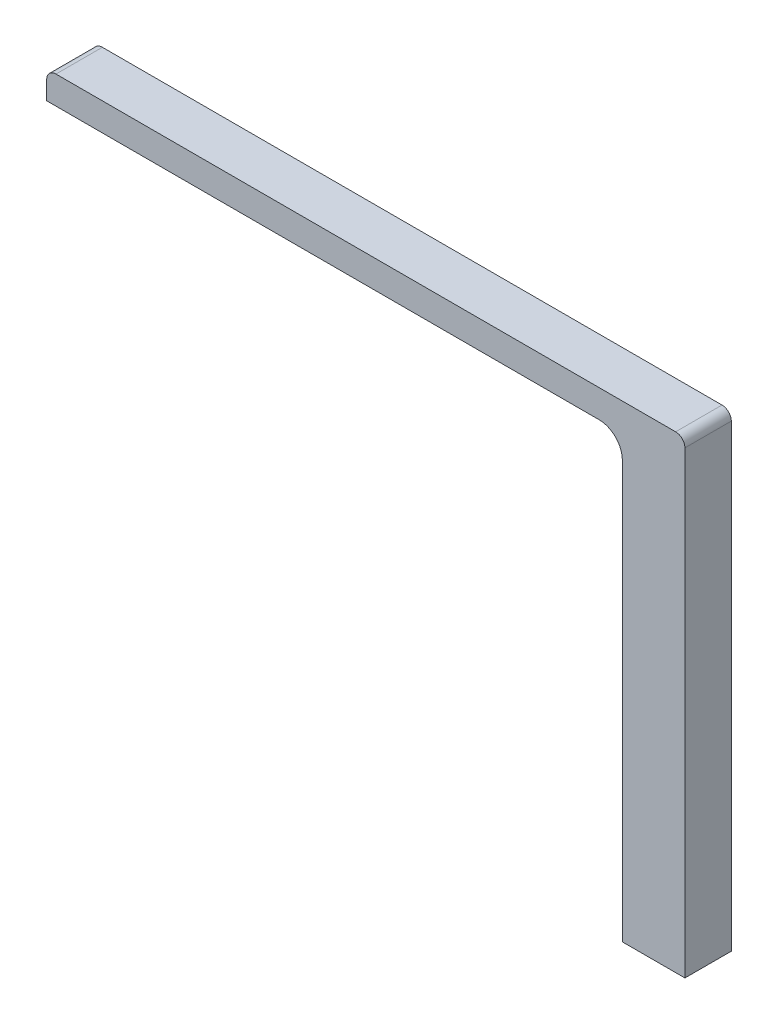
SolidWorks part; units mm, degrees
ref_plane "Front" through (0, 0, 0) normal (0, 0, 1) x (1, 0, 0)
ref_plane "Top" through (0, 0, 0) normal (0, 1, 0) x (1, 0, 0)
ref_plane "Right" through (0, 0, 0) normal (1, 0, 0) x (0, 0, -1)
sketch "Sketch1" plane through (0, 0, 0) normal (0, 0, 1) x (1, 0, 0)
  line L0 (70.2437, -64.135) -> (87.3887, -64.135)
  line L1 (-87.3887, 64.135) -> (87.3887, 64.135)
  line L2 (-87.3887, 64.135) -> (-87.3887, -64.135)
  line L3 (-87.3887, -64.135) -> (-72.6313, -64.135)
  line L4 (87.3887, 64.135) -> (87.3887, -64.135)
  line L5 (-87.3887, 64.135) -> (87.3887, -64.135) construction
  line L6 (-87.3887, -64.135) -> (87.3887, 64.135) construction
  line L7 (70.2437, 56.515) -> (-72.6313, 56.515)
  line L8 (70.2437, 56.515) -> (70.2437, -64.135)
  line L10 (-72.6313, 56.515) -> (-72.6313, -64.135)
  point P0 (0, 0)
  dimension "D1" = 14.7574
  dimension "D2" = 142.875
  dimension "D3" = 7.62
  dimension "D4" = 17.145
  dimension "D5" = 128.27
  dimension "D6" = 174.7774
  dimension "D7" = 128.27
extrude "Boss-Extrude1" add sketch "Sketch1" along normal blind 12.7
fillet "Fillet1" radius 6.35 2 edges at (-72.6313, 56.515, 6.35) (70.2437, 56.515, 6.35)
fillet "Fillet2" radius 2.54 2 edges at (-87.3887, 64.135, 6.35) (87.3887, 64.135, 6.35)
sketch "Sketch2" plane through (0, 0, 0) normal (0, 0, -1) x (-1, 0, 0)
  line L1 (66.2813, 56.515) -> (87.3887, 56.515)
  line L2 (66.2813, 56.515) -> (66.2813, -64.135)
  line L3 (66.2813, -64.135) -> (87.3887, -64.135)
  line L4 (87.3887, 56.515) -> (87.3887, -64.135)
extrude "Cut-Extrude1" cut sketch "Sketch2" against normal through all
